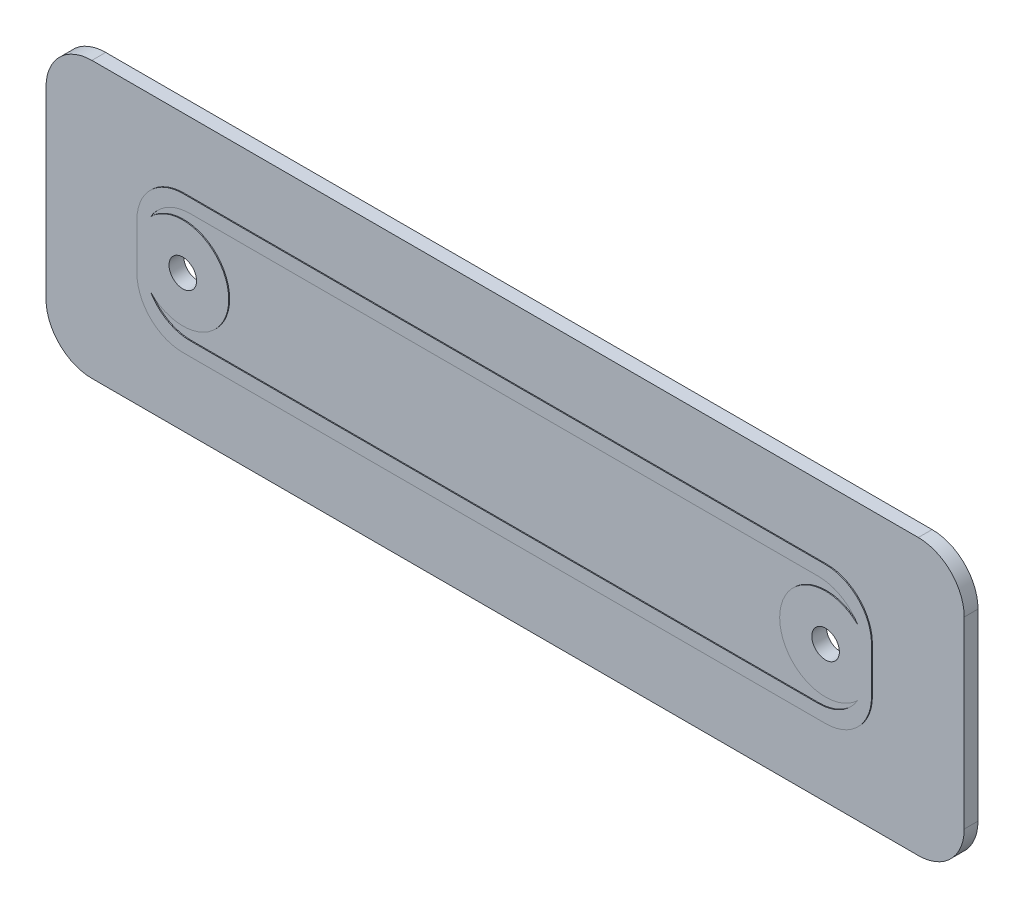
SolidWorks part; units mm, degrees
ref_plane "Front Plane" through (0, 0, 0) normal (0, 0, 1) x (1, 0, 0)
ref_plane "Top Plane" through (0, 0, 0) normal (0, 1, 0) x (1, 0, 0)
ref_plane "Right Plane" through (0, 0, 0) normal (1, 0, 0) x (0, 0, -1)
sketch "Sketch1" plane through (0, 0, 0) normal (0, 0, 1) x (1, 0, 0)
  line L1 (-50, 15) -> (50, 15)
  line L2 (-50, 15) -> (-50, -15)
  line L3 (-50, -15) -> (50, -15)
  line L4 (50, 15) -> (50, -15)
  line L5 (-50, 15) -> (50, -15) construction
  line L6 (-50, -15) -> (50, 15) construction
  point P0 (0, 0)
  dimension "D1" = 100
  dimension "D2" = 30
extrude "Boss-Extrude1" add sketch "Sketch1" along normal blind 1.5
sketch "Sketch2" plane through (0, 0, 1.5) normal (0, 0, 1) x (1, 0, 0)
  line L1 (-40, 7.5) -> (40, 7.5)
  line L2 (-40, 7.5) -> (-40, -7.5)
  line L3 (-40, -7.5) -> (40, -7.5)
  line L4 (40, 7.5) -> (40, -7.5)
  line L5 (-40, 7.5) -> (40, -7.5) construction
  line L6 (-40, -7.5) -> (40, 7.5) construction
  point P0 (0, 0)
  dimension "D1" = 80
  dimension "D2" = 15
extrude "Extrude-Thin1" add sketch "Sketch2" along normal blind 0.1 thin thin type one direction reverse wall 1.5
sketch "Sketch3" plane through (0, 0, 1.5) normal (0, 0, 1) x (1, 0, 0)
  line L0 (0, 12.3228) -> (0, -10.7897) construction
  circle A0 centre (-35, 0) radius 5
  circle A1 centre (35, 0) radius 5
  dimension "D1" = 10
  dimension "D2" = 35
extrude "Boss-Extrude2" add sketch "Sketch3" along normal up to surface (0.1 mm away) up to face at (0, 0, 1.6)
sketch "Sketch4" plane through (0, 0, 1.6) normal (0, 0, 1) x (1, 0, 0)
  line L0 (0, 11.031) -> (0, -19.5989) construction
  circle A0 centre (-35, 0) radius 1.5
  circle A1 centre (35, 0) radius 1.5
  dimension "D1" = 3
extrude "Cut-Extrude1" cut sketch "Sketch4" against normal through all both and the other way through all
fillet "Fillet1" radius 5 12 edges at (40, 7.5, 1.55) (40, -7.5, 1.55) (-40, 7.5, 1.55) (-40, -7.5, 1.55) (-50, 15, 0.75) (-50, -15, 0.75) (50, -15, 0.75) (50, 15, 0.75) (38.5, -6, 1.55) (38.5, 6, 1.55) (-38.5, -6, 1.55) (-38.5, 6, 1.55)
